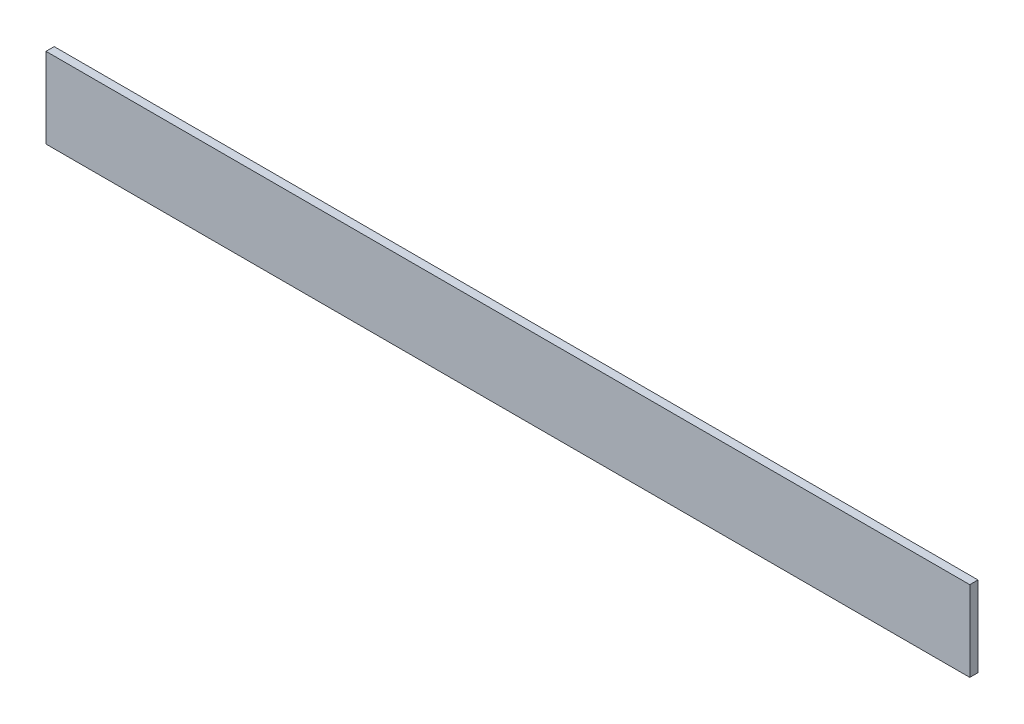
SolidWorks part; units mm, degrees
ref_plane "Front Plane" through (0, 0, 0) normal (0, 0, 1) x (1, 0, 0)
ref_plane "Top Plane" through (0, 0, 0) normal (0, 1, 0) x (1, 0, 0)
ref_plane "Right Plane" through (0, 0, 0) normal (1, 0, 0) x (0, 0, -1)
sketch "Sketch1" plane through (0, 0, 0) normal (0, 0, 1) x (1, 0, 0)
  line L1 (-253, -22) -> (253, -22)
  line L2 (-253, -22) -> (-253, 22)
  line L3 (-253, 22) -> (253, 22)
  line L4 (253, -22) -> (253, 22)
  line L5 (-253, -22) -> (253, 22) construction
  line L6 (-253, 22) -> (253, -22) construction
  point P0 (0, 0)
  point P9 (0, 0)
  dimension "D1" = 506
  dimension "D2" = 44
extrude "Boss-Extrude1" add sketch "Sketch1" along normal blind 4.5
